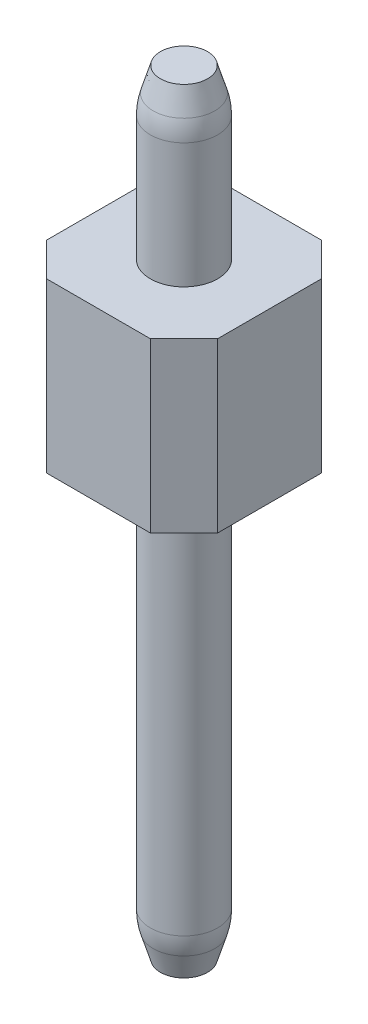
SolidWorks part; units mm, degrees
material "Brass"
ref_plane "Front Plane" through (0, 0, 0) normal (0, 0, 1) x (1, 0, 0)
ref_plane "Top Plane" through (0, 0, 0) normal (0, 1, 0) x (1, 0, 0)
ref_plane "Right Plane" through (0, 0, 0) normal (1, 0, 0) x (0, 0, -1)
sketch "Sketch1" plane through (0, 0, 0) normal (0, 1, 0) x (1, 0, 0)
  line L0 (0, 0) -> (2.54, 0) construction
  circle A0 centre (0, 0) radius 0.5
  circle A1 centre (2.54, 0) radius 0.5
  circle A2 centre (5.08, 0) radius 0.5
  circle A3 centre (7.62, 0) radius 0.5
  circle A4 centre (10.16, 0) radius 0.5
  circle A5 centre (12.7, 0) radius 0.5
  circle A6 centre (15.24, 0) radius 0.5
  circle A7 centre (17.78, 0) radius 0.5
  circle A8 centre (20.32, 0) radius 0.5
  circle A9 centre (22.86, 0) radius 0.5
  circle A10 centre (25.4, 0) radius 0.5
  circle A11 centre (27.94, 0) radius 0.5
  circle A12 centre (30.48, 0) radius 0.5
  circle A13 centre (33.02, 0) radius 0.5
  circle A14 centre (35.56, 0) radius 0.5
  circle A15 centre (38.1, 0) radius 0.5
  dimension "D1" = 1
  dimension "D3" = 2.54
  dimension "D2" = 16
extrude "Boss-Extrude1" add sketch "Sketch1" along normal blind 11.5
ref_plane "Plane1" through (0, 6.5, 0) normal (0, 1, 0) x (1, 0, 0)
sketch "Sketch2" plane through (0, 6.5, 0) normal (0, 1, 0) x (1, 0, 0)
  line L0 (-1.27, 0.77) -> (-0.77, 1.27)
  line L1 (-0.77, -1.27) -> (0.77, -1.27)
  line L2 (-1.27, -0.77) -> (-1.27, 0.77)
  line L3 (-0.77, 1.27) -> (0.77, 1.27)
  line L5 (-1.27, -1.27) -> (1.27, 1.27) construction
  line L6 (-1.27, 1.27) -> (1.27, -1.27) construction
  line L7 (0.77, 1.27) -> (1.27, 0.77)
  line L8 (0.77, -1.27) -> (1.27, -0.77)
  line L9 (-1.27, -0.77) -> (-0.77, -1.27)
  line L10 (1.27, 0.77) -> (1.77, 1.27)
  line L11 (1.77, 1.27) -> (3.31, 1.27)
  line L12 (3.31, 1.27) -> (3.81, 0.77)
  line L14 (3.31, -1.27) -> (3.81, -0.77)
  line L15 (1.77, -1.27) -> (3.31, -1.27)
  line L16 (1.27, -0.77) -> (1.77, -1.27)
  line L17 (3.81, 0.77) -> (4.31, 1.27)
  line L18 (4.31, 1.27) -> (5.85, 1.27)
  line L19 (5.85, 1.27) -> (6.35, 0.77)
  line L20 (6.35, -0.77) -> (6.35, 0.77) construction
  line L21 (5.85, -1.27) -> (6.35, -0.77)
  line L22 (4.31, -1.27) -> (5.85, -1.27)
  line L23 (3.81, -0.77) -> (4.31, -1.27)
  line L24 (6.35, 0.77) -> (6.85, 1.27)
  line L25 (6.85, 1.27) -> (8.39, 1.27)
  line L26 (8.39, 1.27) -> (8.89, 0.77)
  line L27 (8.89, -0.77) -> (8.89, 0.77) construction
  line L28 (8.39, -1.27) -> (8.89, -0.77)
  line L29 (6.85, -1.27) -> (8.39, -1.27)
  line L30 (6.35, -0.77) -> (6.85, -1.27)
  line L31 (8.89, 0.77) -> (9.39, 1.27)
  line L32 (9.39, 1.27) -> (10.93, 1.27)
  line L33 (10.93, 1.27) -> (11.43, 0.77)
  line L34 (11.43, -0.77) -> (11.43, 0.77) construction
  line L35 (10.93, -1.27) -> (11.43, -0.77)
  line L36 (9.39, -1.27) -> (10.93, -1.27)
  line L37 (8.89, -0.77) -> (9.39, -1.27)
  line L38 (11.43, 0.77) -> (11.93, 1.27)
  line L39 (11.93, 1.27) -> (13.47, 1.27)
  line L40 (13.47, 1.27) -> (13.97, 0.77)
  line L41 (13.97, -0.77) -> (13.97, 0.77) construction
  line L42 (13.47, -1.27) -> (13.97, -0.77)
  line L43 (11.93, -1.27) -> (13.47, -1.27)
  line L44 (11.43, -0.77) -> (11.93, -1.27)
  line L45 (13.97, 0.77) -> (14.47, 1.27)
  line L46 (14.47, 1.27) -> (16.01, 1.27)
  line L47 (16.01, 1.27) -> (16.51, 0.77)
  line L48 (16.51, -0.77) -> (16.51, 0.77) construction
  line L49 (16.01, -1.27) -> (16.51, -0.77)
  line L50 (14.47, -1.27) -> (16.01, -1.27)
  line L51 (13.97, -0.77) -> (14.47, -1.27)
  line L52 (16.51, 0.77) -> (17.01, 1.27)
  line L53 (17.01, 1.27) -> (18.55, 1.27)
  line L54 (18.55, 1.27) -> (19.05, 0.77)
  line L55 (19.05, -0.77) -> (19.05, 0.77) construction
  line L56 (18.55, -1.27) -> (19.05, -0.77)
  line L57 (17.01, -1.27) -> (18.55, -1.27)
  line L58 (16.51, -0.77) -> (17.01, -1.27)
  line L59 (19.05, 0.77) -> (19.55, 1.27)
  line L60 (19.55, 1.27) -> (21.09, 1.27)
  line L61 (21.09, 1.27) -> (21.59, 0.77)
  line L62 (21.59, -0.77) -> (21.59, 0.77) construction
  line L63 (21.09, -1.27) -> (21.59, -0.77)
  line L64 (19.55, -1.27) -> (21.09, -1.27)
  line L65 (19.05, -0.77) -> (19.55, -1.27)
  line L66 (21.59, 0.77) -> (22.09, 1.27)
  line L67 (22.09, 1.27) -> (23.63, 1.27)
  line L68 (23.63, 1.27) -> (24.13, 0.77)
  line L69 (24.13, -0.77) -> (24.13, 0.77) construction
  line L70 (23.63, -1.27) -> (24.13, -0.77)
  line L71 (22.09, -1.27) -> (23.63, -1.27)
  line L72 (21.59, -0.77) -> (22.09, -1.27)
  line L73 (24.13, 0.77) -> (24.63, 1.27)
  line L74 (24.63, 1.27) -> (26.17, 1.27)
  line L75 (26.17, 1.27) -> (26.67, 0.77)
  line L76 (26.67, -0.77) -> (26.67, 0.77) construction
  line L77 (26.17, -1.27) -> (26.67, -0.77)
  line L78 (24.63, -1.27) -> (26.17, -1.27)
  line L79 (24.13, -0.77) -> (24.63, -1.27)
  line L80 (26.67, 0.77) -> (27.17, 1.27)
  line L81 (27.17, 1.27) -> (28.71, 1.27)
  line L82 (28.71, 1.27) -> (29.21, 0.77)
  line L83 (29.21, -0.77) -> (29.21, 0.77) construction
  line L84 (28.71, -1.27) -> (29.21, -0.77)
  line L85 (27.17, -1.27) -> (28.71, -1.27)
  line L86 (26.67, -0.77) -> (27.17, -1.27)
  line L87 (29.21, 0.77) -> (29.71, 1.27)
  line L88 (29.71, 1.27) -> (31.25, 1.27)
  line L89 (31.25, 1.27) -> (31.75, 0.77)
  line L90 (31.75, -0.77) -> (31.75, 0.77) construction
  line L91 (31.25, -1.27) -> (31.75, -0.77)
  line L92 (29.71, -1.27) -> (31.25, -1.27)
  line L93 (29.21, -0.77) -> (29.71, -1.27)
  line L94 (31.75, 0.77) -> (32.25, 1.27)
  line L95 (32.25, 1.27) -> (33.79, 1.27)
  line L96 (33.79, 1.27) -> (34.29, 0.77)
  line L97 (34.29, -0.77) -> (34.29, 0.77) construction
  line L98 (33.79, -1.27) -> (34.29, -0.77)
  line L99 (32.25, -1.27) -> (33.79, -1.27)
  line L100 (31.75, -0.77) -> (32.25, -1.27)
  line L101 (34.29, 0.77) -> (34.79, 1.27)
  line L102 (34.79, 1.27) -> (36.33, 1.27)
  line L103 (36.33, 1.27) -> (36.83, 0.77)
  line L104 (36.83, -0.77) -> (36.83, 0.77) construction
  line L105 (36.33, -1.27) -> (36.83, -0.77)
  line L106 (34.79, -1.27) -> (36.33, -1.27)
  line L107 (34.29, -0.77) -> (34.79, -1.27)
  line L108 (36.83, 0.77) -> (37.33, 1.27)
  line L109 (37.33, 1.27) -> (38.87, 1.27)
  line L110 (38.87, 1.27) -> (39.37, 0.77)
  line L111 (39.37, -0.77) -> (39.37, 0.77)
  line L112 (38.87, -1.27) -> (39.37, -0.77)
  line L113 (37.33, -1.27) -> (38.87, -1.27)
  line L114 (36.83, -0.77) -> (37.33, -1.27)
  line L115 (-1.27, 0.77) -> (1.27, 0.77) construction
  point P0 (0, 0)
  dimension "D1" = 2.54
  dimension "D2" = 2.54
  dimension "D4" = 2.54
  dimension "D3" = 16
extrude "Boss-Extrude2" add sketch "Sketch2" along normal blind 2.5
chamfer "Chamfer1" distance 0.5 distance2 0.15 16 edges at (15.24, 11.5, 0.5) (12.7, 11.5, 0.5) (10.16, 11.5, 0.5) (7.62, 11.5, 0.5) (5.08, 11.5, 0.5) (2.54, 11.5, 0.5) (0, 11.5, 0.5) (38.1, 11.5, 0.5) (35.56, 11.5, 0.5) (33.02, 11.5, 0.5) (30.48, 11.5, 0.5) (27.94, 11.5, 0.5) (25.4, 11.5, 0.5) (22.86, 11.5, 0.5) (20.32, 11.5, 0.5) (17.78, 11.5, 0.5) first distance on face at (15.24, 11.5, 0.5) first distance on face at (12.7, 11.5, 0.5) first distance on face at (10.16, 11.5, 0.5) first distance on face at (7.62, 11.5, 0.5) first distance on face at (5.08, 11.5, 0.5) first distance on face at (2.54, 11.5, 0.5) first distance on face at (0, 11.5, 0.5) first distance on face at (38.1, 11.5, 0.5) first distance on face at (35.56, 11.5, 0.5) first distance on face at (33.02, 11.5, 0.5) first distance on face at (30.48, 11.5, 0.5) first distance on face at (27.94, 11.5, 0.5) first distance on face at (25.4, 11.5, 0.5) first distance on face at (22.86, 11.5, 0.5) first distance on face at (20.32, 11.5, 0.5) first distance on face at (17.78, 11.5, 0.5)
fillet "Fillet1" radius 1 16 edges at (38.1, 11, 0.5) (35.56, 11, 0.5) (33.02, 11, 0.5) (30.48, 11, 0.5) (27.94, 11, 0.5) (25.4, 11, 0.5) (22.86, 11, 0.5) (20.32, 11, 0.5) (17.78, 11, 0.5) (15.24, 11, 0.5) (12.7, 11, 0.5) (10.16, 11, 0.5) (7.62, 11, 0.5) (5.08, 11, 0.5) (2.54, 11, 0.5) (0, 11, 0.5)
chamfer "Chamfer2" distance 0.15 distance2 0.5 16 edges at (10.16, 0, 0.5) (17.78, 0, 0.5) (22.86, 0, 0.5) (27.94, 0, 0.5) (30.48, 0, 0.5) (0, 0, 0.5) (2.54, 0, 0.5) (5.08, 0, 0.5) (7.62, 0, 0.5) (12.7, 0, 0.5) (15.24, 0, 0.5) (20.32, 0, 0.5) (25.4, 0, 0.5) (33.02, 0, 0.5) (35.56, 0, 0.5) (38.1, 0, 0.5) first distance on face at (10.16, 0, 0.5) first distance on face at (17.78, 0, 0.5) first distance on face at (22.86, 0, 0.5) first distance on face at (27.94, 0, 0.5) first distance on face at (30.48, 0, 0.5) first distance on face at (0, 0, 0.5) first distance on face at (2.54, 0, 0.5) first distance on face at (5.08, 0, 0.5) first distance on face at (7.62, 0, 0.5) first distance on face at (12.7, 0, 0.5) first distance on face at (15.24, 0, 0.5) first distance on face at (20.32, 0, 0.5) first distance on face at (25.4, 0, 0.5) first distance on face at (33.02, 0, 0.5) first distance on face at (35.56, 0, 0.5) first distance on face at (38.1, 0, 0.5)
fillet "Fillet2" radius 1 16 edges at (30.48, 0.5, 0.5) (33.02, 0.5, 0.5) (35.56, 0.5, 0.5) (38.1, 0.5, 0.5) (27.94, 0.5, 0.5) (25.4, 0.5, 0.5) (22.86, 0.5, 0.5) (20.32, 0.5, 0.5) (17.78, 0.5, 0.5) (15.24, 0.5, 0.5) (12.7, 0.5, 0.5) (10.16, 0.5, 0.5) (7.62, 0.5, 0.5) (5.08, 0.5, 0.5) (2.54, 0.5, 0.5) (0, 0.5, 0.5)
sketch "Sketch3" plane through (0, 0, 1.27) normal (0, 0, 1) x (1, 0, 0)
  line L2 (1.27, 9) -> (1.27, 6.5) construction
  line L3 (1.27, 11.5) -> (1.27, 0)
  line L4 (1.27, 11.5) -> (39.37, 11.5)
  line L5 (39.37, 11.5) -> (39.37, 0)
  line L6 (39.37, 0) -> (1.27, 0)
extrude "Cut-Extrude1" cut sketch "Sketch3" against normal through all both and the other way through all
